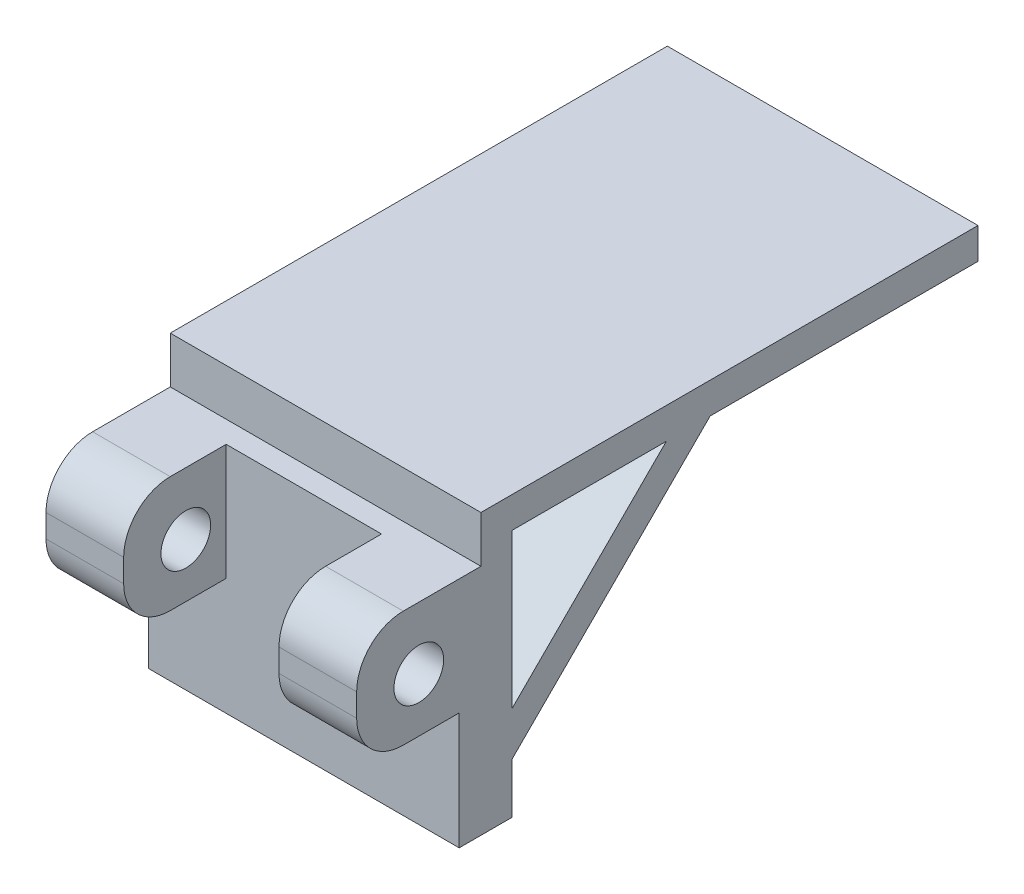
SolidWorks part; units mm, degrees
ref_plane "Front Plane" through (0, 0, 0) normal (0, 0, 1) x (1, 0, 0)
ref_plane "Top Plane" through (0, 0, 0) normal (0, 1, 0) x (1, 0, 0)
ref_plane "Right Plane" through (0, 0, 0) normal (1, 0, 0) x (0, 0, -1)
sketch "Sketch1" plane through (0, 0, 0) normal (0, 0, 1) x (1, 0, 0)
  line L0 (0, 0) -> (0, 7.5) construction
  line L1 (-10, -7.5) -> (10, -7.5)
  line L2 (-10, -7.5) -> (-10, 7.5)
  line L3 (-10, 7.5) -> (10, 7.5)
  line L4 (10, -7.5) -> (10, 7.5)
  line L5 (-10, -7.5) -> (10, 7.5) construction
  line L6 (-10, 7.5) -> (10, -7.5) construction
  line L7 (-5, 7.5) -> (5, 7.5)
  line L8 (-5, 7.5) -> (-5, 0)
  line L9 (-5, 0) -> (5, 0)
  line L10 (5, 7.5) -> (5, 0)
  point P0 (0, 0)
  dimension "D1" = 15
  dimension "D2" = 10
  dimension "D3" = 20
extrude "Boss-Extrude1" add sketch "Sketch1" along normal blind 8 contours L3 L10 L9 L8 L2 L1 L4 region at (0, -1.25, 0)
extrude "Boss-Extrude2" add sketch "Sketch1<3>" against normal blind 2 contours L3 L10 L9 L8 L2 L1 L4 | L10 L3 L8 L9 region at (0, -1.25, 0) region at (0, 3.75, 0)
sketch "Sketch1<3>" plane through (0, 0, 0) normal (0, 0, 1) x (1, 0, 0) same geometry as "Sketch1"
sketch "Sketch2" plane through (10, 0, 0) normal (1, 0, 0) x (0, 0, -1)
  line L0 (-8, 7.5) -> (0, 7.5) construction
  line L1 (-8, 7.5) -> (0, 7.5)
  line L2 (0, 7.5) -> (0, -15) construction
  circle A0 centre (-4, 3.5) radius 1.6
  dimension "D1" = 3.2
  dimension "D2" = 4
  dimension "D3" = 4
extrude "Cut-Extrude1" cut sketch "Sketch2" against normal through all contours A0 region at (10, 3.5, 4)
sketch "Sketch3" plane through (0, 0, 8) normal (0, 0, 1) x (1, 0, 0)
  line L0 (10, 0.0263) -> (-10, 0.0263)
  line L2 (-10, -7.5) -> (-10, 7.5) construction
  line L3 (10, -7.5) -> (10, 7.5) construction
  line L8 (10, 7.5) -> (5, 7.5)
  line L9 (5, 7.5) -> (5, 0)
  line L11 (-5, 0) -> (-5, 7.5)
  line L14 (-10, -7.5) -> (10, -7.5)
  line L15 (5, 0) -> (-5, 0)
  line L16 (10, 7.5) -> (5, 7.5) construction
  line L17 (5, 0.0263) -> (5, 0)
  line L19 (-5, 0) -> (-5, 0.0263)
  line L22 (-10, -7.5) -> (10, -7.5)
  line L24 (5, 0) -> (-5, 0)
  line L25 (-5, 7.5) -> (-10, 7.5)
  line L26 (-5, 7.5) -> (-10, 7.5)
  line L27 (-10, 7.5) -> (-10, -7.5)
  line L28 (-10, 7.5) -> (-10, -7.5)
  line L29 (10, -7.5) -> (10, 7.5)
  line L30 (10, -7.5) -> (10, 7.5)
  line M11 (5, 7.5) -> (5, 0)
  line M12 (5, 0) -> (-5, 0)
  line M13 (-5, 0) -> (-5, 7.5)
  line M15 (-10, 7.5) -> (-10, -7.5)
  line M16 (-10, -7.5) -> (10, -7.5)
  line M17 (10, -7.5) -> (10, 7.5)
  dimension "D1" = 0
extrude "Cut-Extrude3" cut sketch "Sketch3" against normal up to surface (8 mm away) contours L0 M17 M11 M12 M13 M15 M16 region at (0, -3.7434, 8) up to face at (0, 3.75, 0)
fillet "Fillet1" radius 3 4 edges at (-7.5, 0.0263, 8) (-7.5, 7.5, 8) (7.5, 7.5, 8) (7.5, 0.0263, 8)
sketch "Sketch4" plane through (0, 7.5, 0) normal (0, 1, 0) x (1, 0, 0)
  line L0 (-5, 0) -> (5, 0) construction
  line L1 (-10, -5) -> (-10, 2) construction
  line L2 (10, -5) -> (10, 2) construction
  line L3 (-10, 2) -> (10, 2) construction
  line L4 (-5, 0) -> (5, 0)
  line L5 (-10, 0) -> (-10, 2)
  line L6 (10, 0) -> (10, 2)
  line L7 (-10, 2) -> (10, 2)
  line L8 (5, 0) -> (10, 0)
  line L9 (-5, 0) -> (-10, 0)
extrude "Boss-Extrude3" add sketch "Sketch4" along normal blind 3
sketch "Sketch5" plane through (0, 0, -2) normal (0, 0, -1) x (-1, 0, 0)
  line L0 (-10, 10.5) -> (10, 10.5) construction
  line L1 (-10, 10.5) -> (10, 10.5)
  line L2 (-10, 10.5) -> (-10, 8.5)
  line L3 (-10, -7.5) -> (-10, 10.5) construction
  line L4 (-10, 8.5) -> (10, 8.5)
  line L5 (10, -7.5) -> (10, 10.5) construction
  line L6 (10, 8.5) -> (10, 10.5)
  dimension "D1" = 2
extrude "Boss-Extrude4" add sketch "Sketch5" along normal blind 30
sketch "Sketch8" plane through (10, 0, 0) normal (1, 0, 0) x (0, 0, -1)
  line L0 (14.7571, 8.5) -> (11.9346, 8.5)
  line L1 (32, 8.5) -> (2, 8.5) construction
  line L2 (11.9346, 8.5) -> (2, -1.4346)
  line L3 (2, -7.5) -> (2, 8.5) construction
  line L4 (2, -1.4346) -> (2, -4.2571)
  line L5 (2, -4.2571) -> (14.7571, 8.5)
  dimension "D1" = 1.9958
extrude "Boss-Extrude5" add sketch "Sketch8" against normal up to surface (20 mm away) up to face at (-10, 3.7982, -3.3964)
sketch "Sketch9" plane through (0, 0, 0) normal (0, 0, 1) x (1, 0, 0)
  line L0 (-5, 7.5) -> (5, 7.5)
  line L12 (5, 0.0263) -> (5, 7.5)
  line L13 (5, 7.5) -> (10, 7.5)
  line L14 (10, 7.5) -> (10, 10.5)
  line L15 (10, 10.5) -> (-10, 10.5)
  line L16 (-10, 10.5) -> (-10, 7.5)
  line L17 (-10, 7.5) -> (-5, 7.5)
  line L18 (-5, 7.5) -> (-5, 0.0263)
  line L19 (-5, 0.0263) -> (-10, 0.0263)
  line L20 (-10, 0.0263) -> (-10, -7.5)
  line L21 (-10, -7.5) -> (10, -7.5)
  line L22 (10, -7.5) -> (10, 0.0263)
  line L23 (10, 0.0263) -> (5, 0.0263)
  line L24 (5, 0.0263) -> (5, 7.5)
  line L30 (-5, 7.5) -> (-5, 0.0263)
  line L31 (-5, 0.0263) -> (-10, 0.0263)
  line L32 (-10, 0.0263) -> (-10, -7.5)
  line L33 (-10, -7.5) -> (10, -7.5)
  line L34 (10, -7.5) -> (10, 0.0263)
  line L35 (10, 0.0263) -> (5, 0.0263)
  dimension "D1" = 0
extrude "Boss-Extrude6" add sketch "Sketch9" along normal blind 1.4
